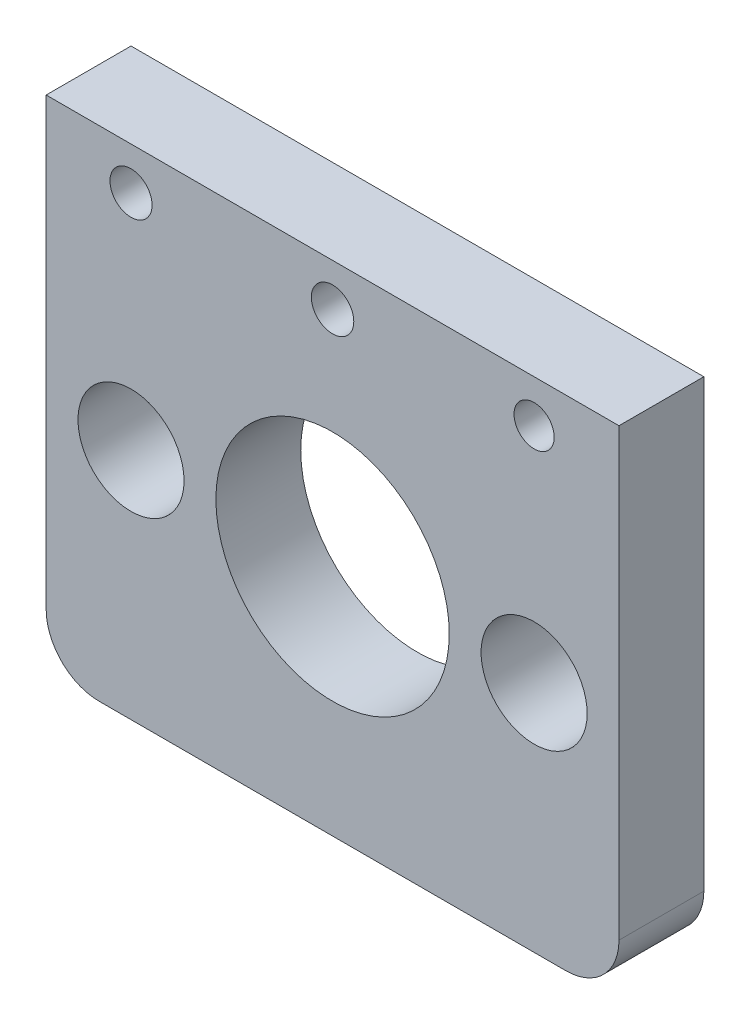
SolidWorks part; units mm, degrees
ref_plane "Front Plane" through (0, 0, 0) normal (0, 0, 1) x (1, 0, 0)
ref_plane "Top Plane" through (0, 0, 0) normal (0, 1, 0) x (1, 0, 0)
ref_plane "Right Plane" through (0, 0, 0) normal (1, 0, 0) x (0, 0, -1)
sketch "Sketch1" plane through (0, 0, 0) normal (0, 0, 1) x (1, 0, 0)
  line L0 (-27, 21) -> (27, 21) construction
  line L1 (-22, -22) -> (22, -22)
  line L2 (-27, -17) -> (-27, 25)
  line L3 (-27, 25) -> (27, 25)
  line L4 (27, -17) -> (27, 25)
  line L5 (0, 25) -> (0, 0) construction
  line L6 (-14.2178, -17.2025) -> (14.2178, -17.2025) construction
  circle A0 centre (-19, 0) radius 5
  circle A1 centre (19, 0) radius 5
  circle A2 centre (0, 0) radius 11
  circle A3 centre (0, 21) radius 2
  circle A4 centre (-19, 21) radius 1.9846
  circle A5 centre (19, 21) radius 1.8944
  arc A6 (22, -22) -> (27, -17) centre (22, -17) ccw
  arc A7 (-22, -22) -> (-27, -17) centre (-22, -17) cw
  point P4 (0, 0)
  point P26 (27, -22)
  point P29 (-27, -22)
  dimension "D1" = 19
  dimension "D4" = 25
  dimension "D7" = 5
  dimension "D2" = 38
  dimension "D3" = 54
  dimension "D5" = 22
  dimension "D6" = 4
extrude "Boss-Extrude1" add sketch "Sketch1" along normal blind 8
